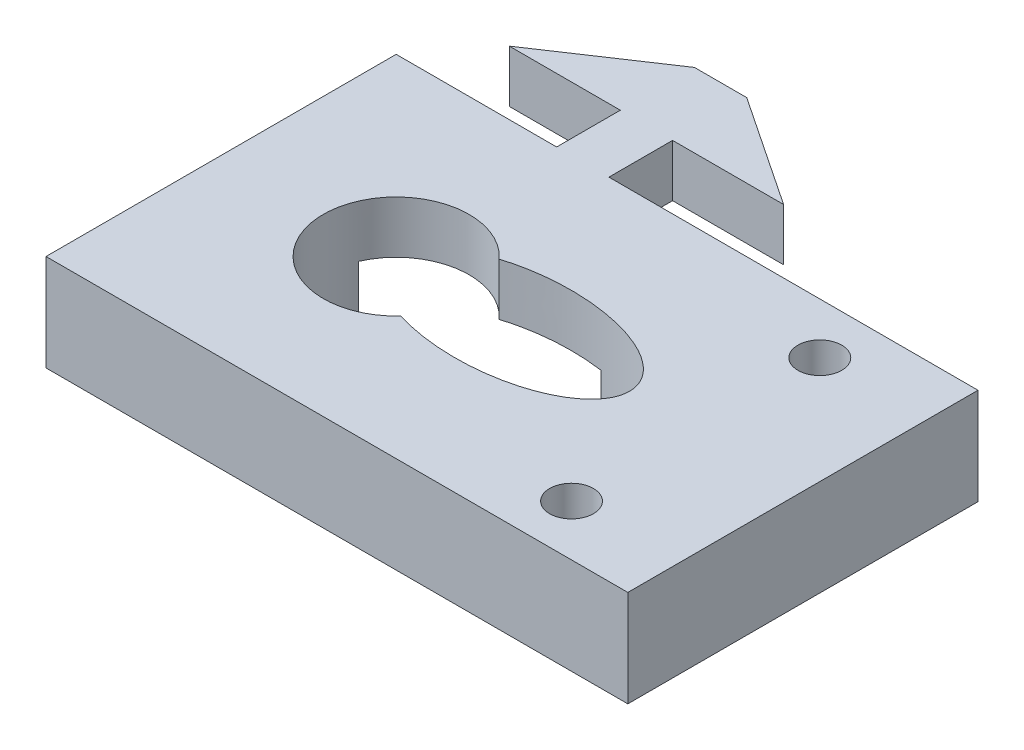
SolidWorks part; units mm, degrees
ref_plane "Front" through (0, 0, 0) normal (0, 0, 1) x (1, 0, 0)
ref_plane "Top" through (0, 0, 0) normal (0, 1, 0) x (1, 0, 0)
ref_plane "Right" through (0, 0, 0) normal (1, 0, 0) x (0, 0, -1)
sketch "Sketch1" plane through (0, 0, 0) normal (0, 1, 0) x (1, 0, 0)
  line L0 (-1.7907, 2.1825) -> (-9.398, 2.1825)
  line L2 (-1.7907, -2.1825) -> (-1.7907, 2.1825)
  line L4 (1.7907, -2.1825) -> (1.7907, 2.1825)
  line L7 (-9.398, 2.1825) -> (-1.7907, 7.2625)
  line L8 (-1.7907, 7.2625) -> (1.7907, 7.2625)
  line L9 (1.7907, 7.2625) -> (9.398, 2.1825)
  line L10 (9.398, 2.1825) -> (1.7907, 2.1825)
  line L11 (1.7907, -2.1825) -> (27.088, -2.1825)
  line L12 (-1.7907, -2.1825) -> (-12.79, -2.1825)
  line L13 (-12.79, -2.1825) -> (-12.79, -26.1825)
  line L14 (-12.79, -26.1825) -> (27.088, -26.1825)
  line L15 (27.088, -26.1825) -> (27.088, -2.1825)
  line L16 (27.088, -2.1825) -> (1.7907, -2.1825)
  point P0 (0, 0)
  point P17 (0, 7.2625)
  point P24 (1.7907, 0)
  dimension "D1" = 18.796
  dimension "D2" = 3.5814
  dimension "D3" = 39.878
  dimension "D4" = 24
  dimension "D5" = 5.08
  dimension "D6" = 12.79
  dimension "D7" = 4.365
extrude "Boss-Extrude1" add sketch "Sketch1" along normal blind 3.5814 contours L14 L15 L11 L4 L10 L9 L8 L7 L0 L2 L12 L13 region at (6.6458, 0, 12.9552)
ref_plane "Plane1" through (0, 1.7907, 0) normal (0, 1, 0) x (1, 0, 0)
sketch "Sketch7" plane through (0, 0, 0) normal (0, 1, 0) x (1, 0, 0)
  line L1 (-12.79, -2.1825) -> (27.088, -2.1825)
  line L2 (-12.79, -2.1825) -> (-12.79, -26.1825)
  line L3 (-12.79, -26.1825) -> (27.088, -26.1825)
  line L4 (27.088, -2.1825) -> (27.088, -26.1825)
extrude "Boss-Extrude2" add sketch "Sketch7" along normal blind 3.035 and the other way blind 3.035
sketch "Sketch5" plane through (0, 3.5814, 0) normal (0, 1, 0) x (1, 0, 0)
  line L0 (-12.79, -2.1825) -> (-12.79, -26.1825) construction
  line L1 (-12.79, -14.1825) -> (27.088, -14.1825) construction
  line L2 (27.088, -26.1825) -> (27.088, -2.1825) construction
  circle A0 centre (-0.79, -14.1825) radius 5
  circle A1 centre (19.738, -22.6915) radius 1.5
  circle A2 centre (19.738, -5.6735) radius 1.5
  ellipse E0 centre (7.21, -14.1825) end of major axis (-0.79, -14.1825) minor radius 4
  point P5 (-12.79, -14.1825)
  point P15 (0, 0)
  point P21 (19.778, -23.1429)
  dimension "D2" = 10
  dimension "D6" = 3
  dimension "D1" = 12
  dimension "D3" = 8
  dimension "D4" = 16
  dimension "D5" = 17.018
  dimension "D7" = 7.35
extrude "Cut-Extrude3" cut sketch "Sketch5" against normal through all both and the other way through all contours A0 L1 E0 | E0 L1 A0 | A0 L1 E0 | L1 A0 E0 | L1 E0 A0 | L1 A0 E0 | A1 | A2 region at (1.9147, 3.5814, 12.8743) region at (-1.952, 3.5814, 16.6542) region at (1.9147, 3.5814, 15.4907) region at (-1.952, 3.5814, 11.7108) region at (8.8346, 3.5814, 12.3654) region at (8.8346, 3.5814, 15.9996) region at (19.738, 3.5814, 22.6915)
ref_plane "Plane2" through (0, 0, -17.2625) normal (0, 0, -1) x (-1, 0, 0)
sketch "Sketch8" plane through (0, 0, 2.1825) normal (0, 0, -1) x (-1, 0, 0)
  line L0 (-27.088, -3.035) -> (12.79, -3.035) construction
  line L1 (-9.398, 0) -> (9.398, 0)
  line L2 (-9.398, 0) -> (-9.398, -3.035)
  line L3 (-9.398, -3.035) -> (9.398, -3.035)
  line L4 (9.398, 0) -> (9.398, -3.035)
  line L5 (-9.398, 3.5814) -> (-9.398, 0) construction
  line L6 (9.398, 3.5814) -> (9.398, 0) construction
  line L7 (-1.7907, 0) -> (1.7907, 0) construction
extrude "Cut-Extrude4" cut sketch "Sketch8" against normal blind 10
